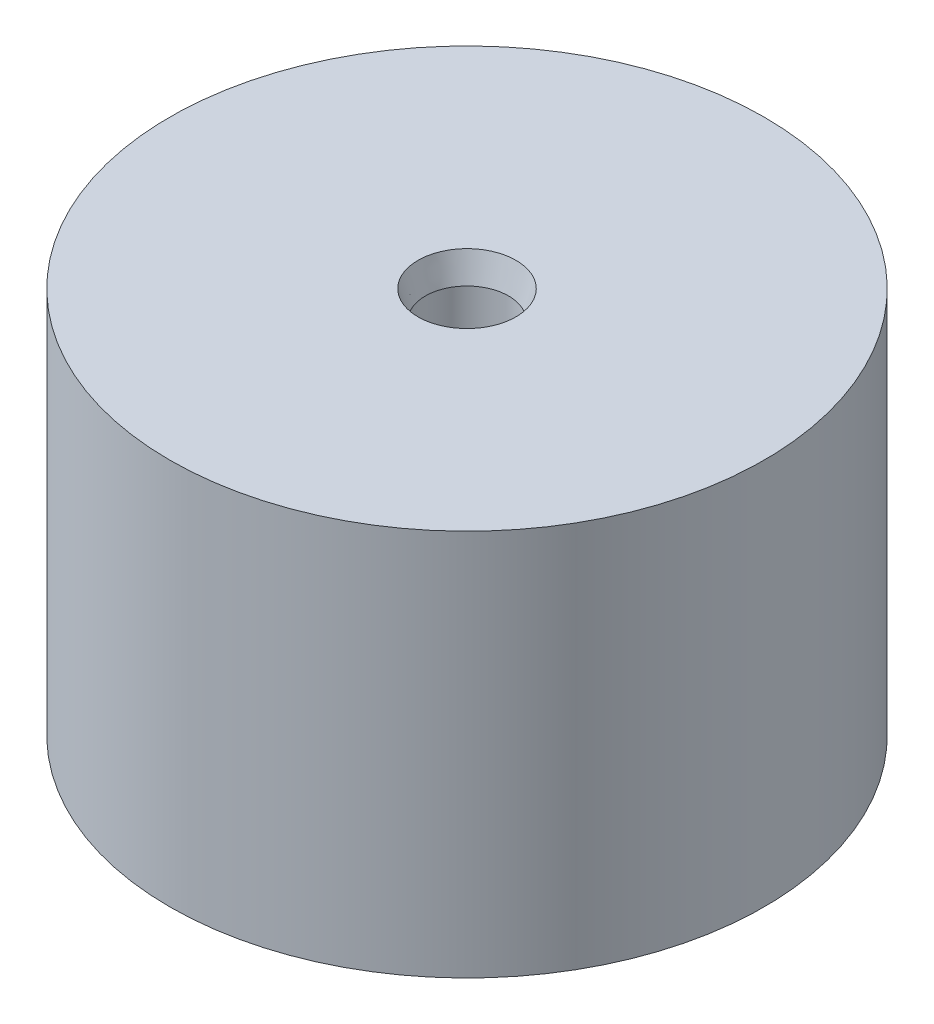
SolidWorks part; units mm, degrees
ref_plane "Front Plane" through (0, 0, 0) normal (0, 0, 1) x (1, 0, 0)
ref_plane "Top Plane" through (0, 0, 0) normal (0, 1, 0) x (1, 0, 0)
ref_plane "Right Plane" through (0, 0, 0) normal (1, 0, 0) x (0, 0, -1)
sketch "Sketch1" plane through (0, 0, 0) normal (0, 0, 1) x (1, 0, 0)
  line L0 (0, 20.7983) -> (0, -18.4168) construction
  line L1 (-12.7012, 0) -> (16.591, 0) construction
  line L2 (-2, 19.6081) -> (-2, -19.1307) construction
  line L3 (-2, 2.5) -> (-2, -2.5)
  line L4 (-2, -2.5) -> (-14.25, -14.75)
  line L5 (-14.25, 20.7983) -> (-14.25, -18.4168) construction
  line L6 (-2, 2.5) -> (-2.35, 3.8062)
  line L7 (-2.35, 3.8062) -> (-14.25, 3.8062)
  line L8 (-14.25, 3.8062) -> (-14.25, -14.75)
  point P10 (-2, 0)
  dimension "D1" = 5
  dimension "D2" = 14.25
  dimension "D3" = 15
  dimension "D4" = 2
  dimension "D5" = 2.35
  dimension "D6" = 45
revolve "Revolve1" add sketch "Sketch1" angle 360 about L0
